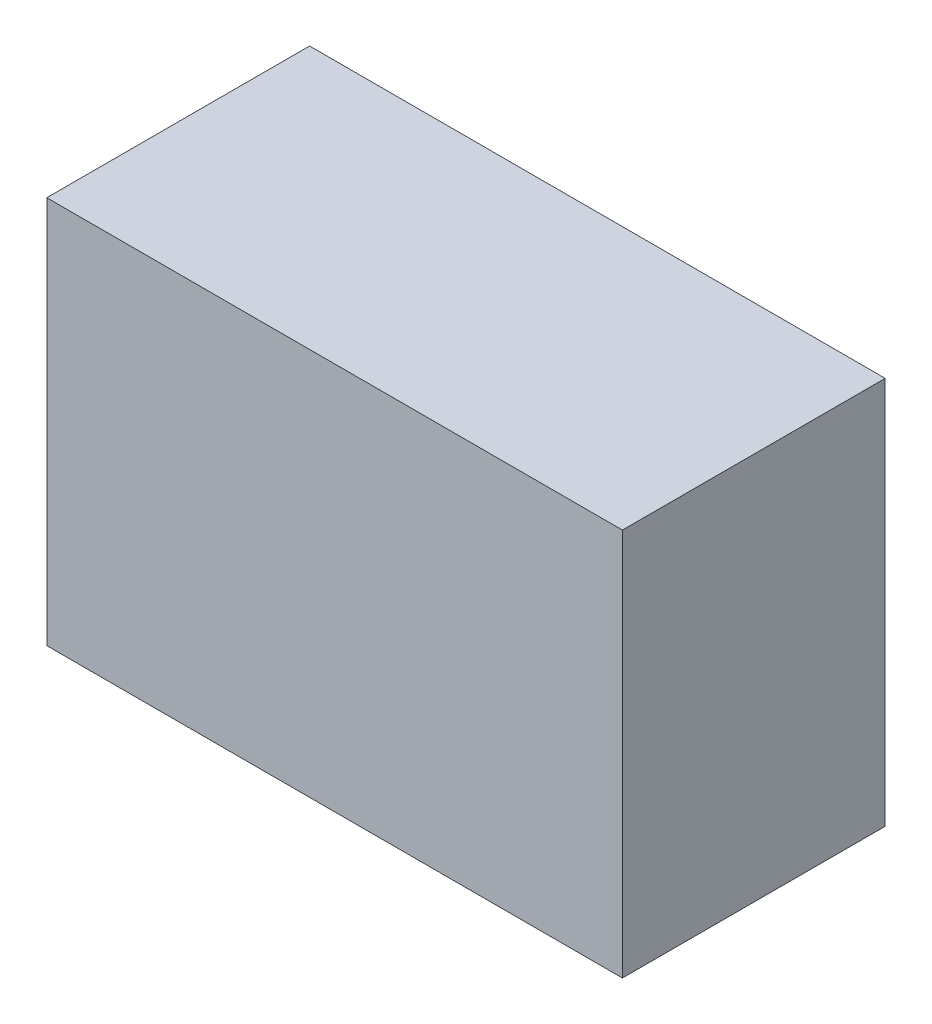
SolidWorks part; units mm, degrees
ref_plane "正面" through (0, 0, 0) normal (0, 0, 1) x (1, 0, 0)
ref_plane "平面" through (0, 0, 0) normal (0, 1, 0) x (1, 0, 0)
ref_plane "右側面" through (0, 0, 0) normal (1, 0, 0) x (0, 0, -1)
sketch "ｽｹｯﾁ1" plane through (0, 0, 0) normal (0, 0, 1) x (1, 0, 0)
  line L1 (0, 0) -> (46, 0)
  line L2 (0, 0) -> (0, 31)
  line L3 (0, 31) -> (46, 31)
  line L4 (46, 0) -> (46, 31)
  dimension "D1" = 46
  dimension "D2" = 31
extrude "ﾎﾞｽ - 押し出し1" add sketch "ｽｹｯﾁ1" along normal blind 21
sketch "ｽｹｯﾁ2" plane through (0, 0, 0) normal (0, -1, 0) x (1, 0, 0)
  line L0 (0, 10.5) -> (-1, 10.5) construction
  line L1 (0, 21) -> (0, 0) construction
  circle A0 centre (-1, 11.5) radius 1
  circle A1 centre (-1, 9.5) radius 1
  dimension "D1" = 2
extrude "ﾎﾞｽ - 押し出し2" add sketch "ｽｹｯﾁ2" along normal blind 5 and the other way blind 5 separate body contours A0 | A1 region at (-1, 0, 11.5) region at (-1, 0, 9.5)
